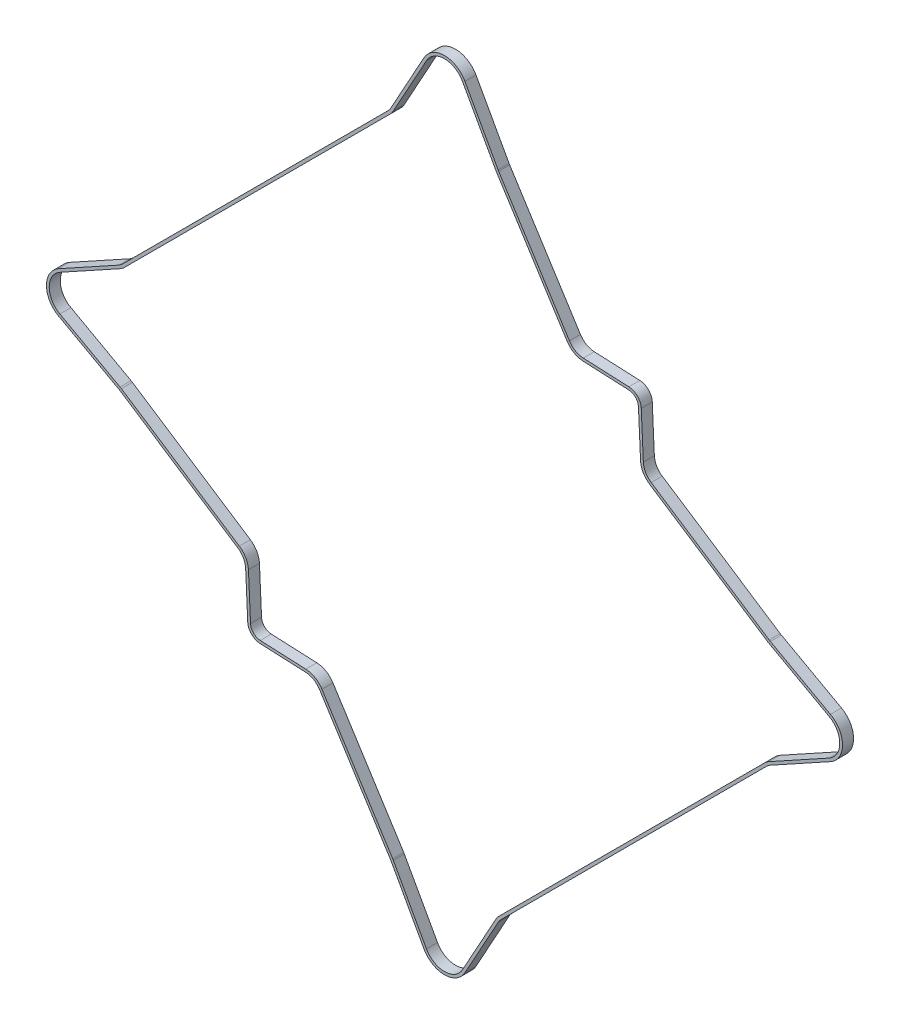
SolidWorks part; units mm, degrees
material "NEOPRENE"
ref_plane "Front Plane" through (0, 0, 0) normal (0, 0, 1) x (1, 0, 0)
ref_plane "Top Plane" through (0, 0, 0) normal (0, 1, 0) x (1, 0, 0)
ref_plane "Right Plane" through (0, 0, 0) normal (1, 0, 0) x (0, 0, -1)
sketch "Sketch2" plane through (0, 0, 0) normal (0, 0, 1) x (1, 0, 0)
  line L0 (0, 0) -> (1, 0) construction
  line L1 (0, 0) -> (0, 1) construction
  line L8 (-144.245, -261.1155) -> (-143.1126, -285.9127)
  line L9 (-137.8097, -291.2156) -> (-113.0125, -292.348)
  line L18 (69.245, -102.8845) -> (68.1126, -78.0873)
  line L19 (62.8097, -72.7844) -> (38.0125, -71.652)
  line L21 (-9.6324, -5.3119) -> (-27.6801, 27.4153)
  line L22 (-47.3199, 27.4153) -> (-65.3676, -5.3119)
  line L23 (-67.2218, -7.7782) -> (-211.7218, -152.2782)
  line L24 (-214.1881, -154.1324) -> (-246.9153, -172.1801)
  line L25 (-246.9153, -191.8199) -> (-214.1881, -209.8676)
  line L26 (-213.4705, -210.2997) -> (-149.2041, -252.417)
  line L27 (-104.2278, -297.4407) -> (-65.7135, -358.1041)
  line L28 (-65.3676, -358.6881) -> (-47.3199, -391.4153)
  line L29 (-27.6801, -391.4153) -> (-9.6324, -358.6881)
  line L30 (-7.7782, -356.2218) -> (136.7218, -211.7218)
  line L31 (139.1881, -209.8676) -> (171.9153, -191.8199)
  line L32 (171.9153, -172.1801) -> (139.1881, -154.1324)
  line L33 (138.4705, -153.7003) -> (74.2041, -111.583)
  line L34 (29.2278, -66.5593) -> (-9.2865, -5.8959)
  arc A0 (-65.3676, -5.3119) -> (-67.2218, -7.7782) centre (-75, 0) cw
  arc A1 (-27.6801, 27.4153) -> (-47.3199, 27.4153) centre (-37.5, 22) ccw
  arc A2 (-9.2865, -5.8959) -> (-9.6324, -5.3119) centre (0, 0) cw
  arc A3 (-214.1881, -209.8676) -> (-213.4705, -210.2997) centre (-219.5, -219.5) cw
  arc A4 (-246.9153, -172.1801) -> (-246.9153, -191.8199) centre (-241.5, -182) ccw
  arc A5 (-211.7218, -152.2782) -> (-214.1881, -154.1324) centre (-219.5, -144.5) cw
  arc A6 (-149.2041, -252.417) -> (-144.245, -261.1155) centre (-155.2336, -261.6173) cw
  arc A7 (-143.1126, -285.9127) -> (-137.8097, -291.2156) centre (-137.5559, -285.6589) ccw
  arc A8 (-113.0125, -292.348) -> (-104.2278, -297.4407) centre (-113.5143, -303.3366) cw
  arc A9 (-9.6324, -358.6881) -> (-7.7782, -356.2218) centre (0, -364) cw
  arc A10 (-47.3199, -391.4153) -> (-27.6801, -391.4153) centre (-37.5, -386) ccw
  arc A11 (-65.7135, -358.1041) -> (-65.3676, -358.6881) centre (-75, -364) cw
  arc A12 (139.1881, -154.1324) -> (138.4705, -153.7003) centre (144.5, -144.5) cw
  arc A13 (171.9153, -191.8199) -> (171.9153, -172.1801) centre (166.5, -182) ccw
  arc A14 (136.7218, -211.7218) -> (139.1881, -209.8676) centre (144.5, -219.5) cw
  arc A15 (74.2041, -111.583) -> (69.245, -102.8845) centre (80.2336, -102.3827) cw
  arc A16 (68.1126, -78.0873) -> (62.8097, -72.7844) centre (62.5559, -78.3411) ccw
  arc A17 (38.0125, -71.652) -> (29.2278, -66.5593) centre (38.5143, -60.6634) cw
extrude "Extrude-Thin1" add sketch "Sketch2" along normal mid plane 6 thin thin type one direction wall 1.52
